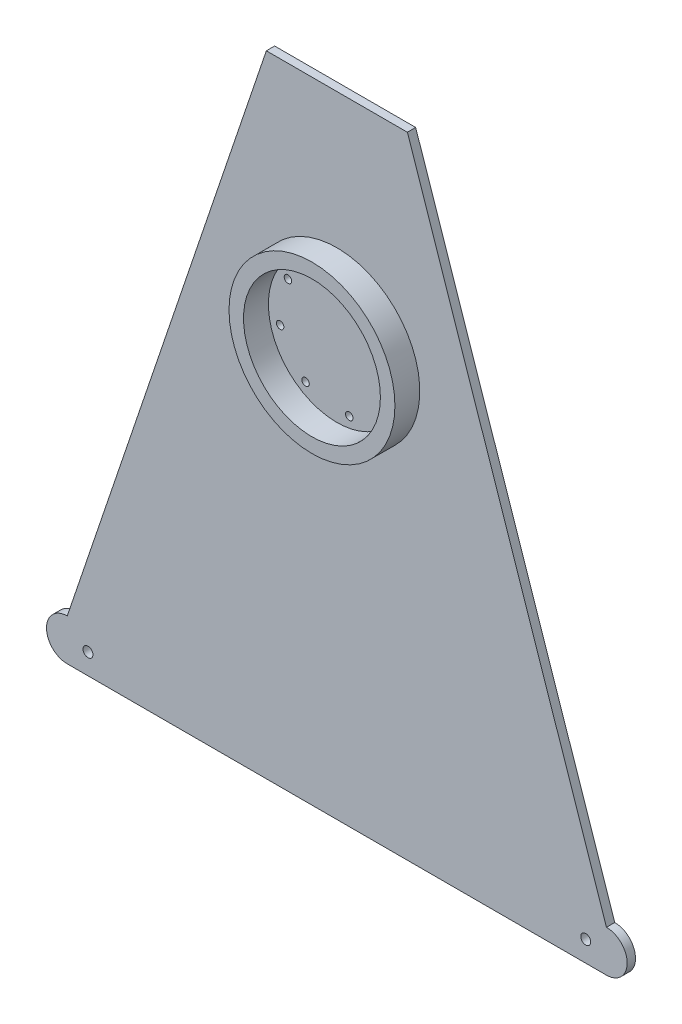
SolidWorks part; units mm, degrees
ref_plane "Front Plane" through (0, 0, 0) normal (0, 0, 1) x (1, 0, 0)
ref_plane "Top Plane" through (0, 0, 0) normal (0, 1, 0) x (1, 0, 0)
ref_plane "Right Plane" through (0, 0, 0) normal (1, 0, 0) x (0, 0, -1)
sketch "Sketch1" plane through (0, 0, 0) normal (0, 0, 1) x (1, 0, 0)
  line L1 (-350, -25) -> (350, -25)
  line L2 (-350, -25) -> (-350, 25)
  line L3 (-350, 25) -> (350, 25)
  line L4 (350, -25) -> (350, 25)
  line L5 (-350, -25) -> (350, 25) construction
  line L6 (-350, 25) -> (350, -25) construction
  circle A0 centre (-300, 0) radius 6
  circle A1 centre (300, 0) radius 6
  point P0 (0, 0)
  dimension "D3" = 12
  dimension "D5" = 12
  dimension "D1" = 700
  dimension "D2" = 50
  dimension "D4" = 50
  dimension "D6" = 50
extrude "Boss-Extrude1" add sketch "Sketch1" along normal blind 10
fillet "Fillet1" 2 edges at (-350, 25, 5) (-350, -25, 5) type full round first side face at (0, 25, 5) second side face at (0, -25, 5) middle face at (-350, 0, 5)
fillet "Fillet2" 2 edges at (350, 25, 5) (350, -25, 5) type full round first side face at (12.5, 25, 5) second side face at (12.5, -25, 5) middle face at (350, 0, 5)
sketch "Sketch2" plane through (0, 0, 10) normal (0, 0, 1) x (1, 0, 0)
  line L0 (-325, 25) -> (-85, 735)
  line L1 (-85, 735) -> (85, 735)
  line L2 (85, 735) -> (325, 25)
  line L5 (-325, -25) -> (325, -25) construction
  line L6 (-325, 25) -> (325, 25)
  point P3 (0, 735)
  dimension "D1" = 760
  dimension "D2" = 170
extrude "Boss-Extrude2" add sketch "Sketch2" against normal up to surface (10 mm away) up to face at (-294, 0, 0)
sketch "Sketch3" plane through (0, 0, 10) normal (0, 0, 1) x (1, 0, 0)
  line L0 (85, 735) -> (-85, 735) construction
  circle A0 centre (0, 472) radius 100
  circle A1 centre (0, 472) radius 82.5
  dimension "D1" = 200
  dimension "D3" = 165
  dimension "D2" = 263
extrude "Boss-Extrude3" add sketch "Sketch3" along normal blind 30
sketch "Sketch4" plane through (0, 0, 10) normal (0, 0, 1) x (1, 0, 0)
  circle A0 centre (0, 472) radius 70
  circle A1 centre (-37.7392, 413.0445) radius 4.5
  dimension "D1" = 140
  dimension "D2" = 9
extrude "Cut-Extrude1" cut sketch "Sketch4" against normal through all contours A0 A1 | A0 A1 region at (-36.6956, 414.6748, 10) region at (-38.7547, 411.4581, 10)
pattern_circular "CirPattern1" count 8 over 360 about axis through (0, 472, 10) along (0, 0, 1) of "Cut-Extrude1"
